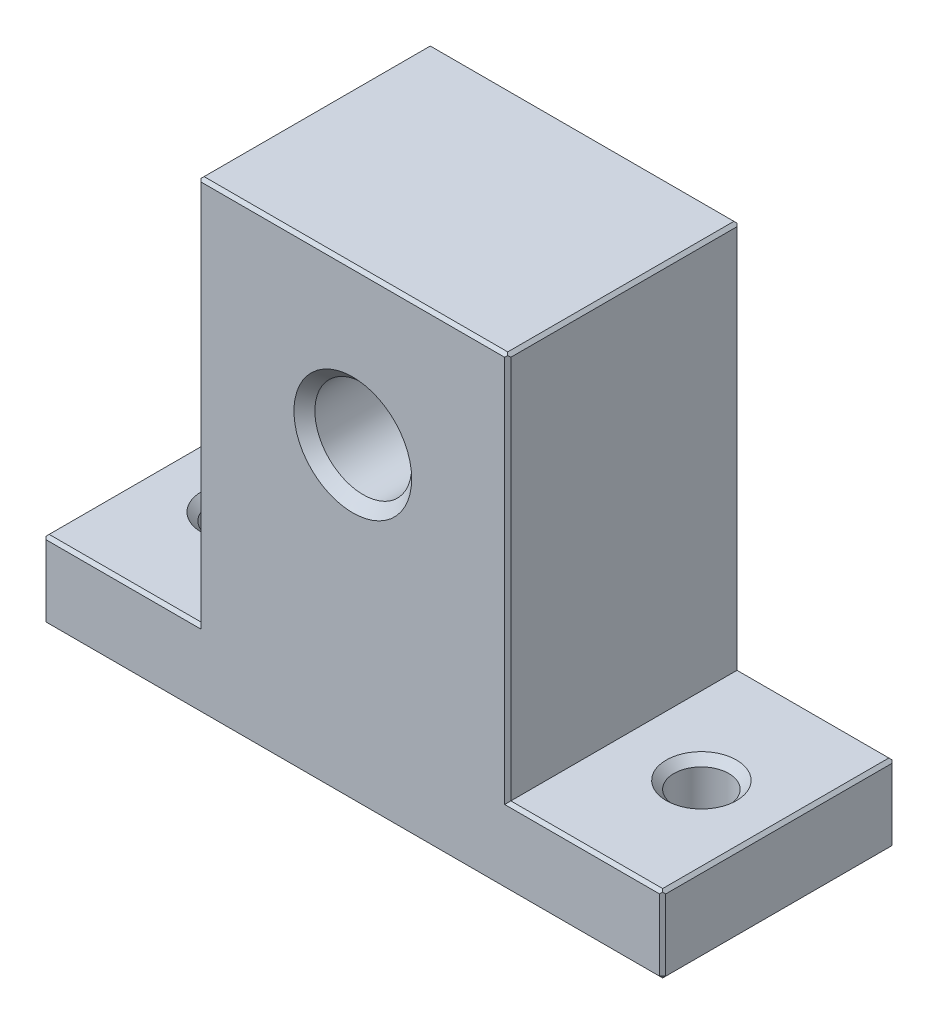
SolidWorks part; units mm, degrees
material "6061-T6 (SS)"
ref_plane "Front Plane" through (0, 0, 0) normal (0, 0, 1) x (1, 0, 0)
ref_plane "Top Plane" through (0, 0, 0) normal (0, 1, 0) x (1, 0, 0)
ref_plane "Right Plane" through (0, 0, 0) normal (1, 0, 0) x (0, 0, -1)
ref_axis "X Axis" through (88.99, 0, 0) along (-1, 0, 0)
ref_axis "Y Axis" through (0, 55, 0) along (0, -1, 0)
ref_axis "Z Axis" through (0, 0, -88.99) along (0, 0, 1)
sketch "Sketch1" plane through (0, 0, 0) normal (0, 1, 0) x (1, 0, 0)
  line L1 (-25.4, -9.525) -> (25.4, -9.525)
  line L2 (-25.4, -9.525) -> (-25.4, 9.525)
  line L3 (-25.4, 9.525) -> (25.4, 9.525)
  line L4 (25.4, -9.525) -> (25.4, 9.525)
  line L5 (0, 9.525) -> (0, -9.525) construction
  line L6 (-25.4, 0) -> (25.4, 0) construction
  line L7 (-12.7, -9.525) -> (12.7, -9.525)
  line L8 (-12.7, -9.525) -> (-12.7, 9.525)
  line L9 (-12.7, 9.525) -> (12.7, 9.525)
  line L10 (12.7, -9.525) -> (12.7, 9.525)
  line L11 (0, 9.525) -> (0, -9.525) construction
  line L12 (-12.7, 0) -> (12.7, 0) construction
  point P0 (0, 0)
  point P4 (0, 0)
  dimension "D1" = 19.05
  dimension "D2" = 50.8
  dimension "D3" = 25.4
extrude "Boss-Extrude1" add sketch "Sketch1" along normal blind 6.35 contours L1 L8 L3 L2 | L1 L10 L3 L8 | L10 L1 L4 L3 region at (-19.05, 0, 0) region at (0, 0, 0) region at (19.05, 0, 0)
extrude "Boss-Extrude2" add sketch "Sketch1<3>" along normal blind 38.1 contours L1 L10 L3 L8 region at (0, 0, 0)
sketch "Sketch1<3>" plane through (0, 0, 0) normal (0, 1, 0) x (1, 0, 0) same geometry as "Sketch1"
sketch "Sketch3" plane through (0, 0, 9.525) normal (0, 0, 1) x (1, 0, 0)
  line L0 (0, 0) -> (0, 25.4) construction
  point P1 (0, 25.4)
  point P13 (0, 25.4)
  dimension "D1" = 25.4
hole_wizard "3/8-16 Tapped Hole1" positions "Sketch3" profile "Sketch4" tap size "3/8-16" standard "ANSI Inch" end condition through all
sketch "Sketch4" plane through (0, 25.4, 9.525) normal (1, 0, 0) x (0, -1, 0)
  line L0 (0, 0) -> (0, 19.05)
  line L1 (0, 19.05) -> (4.826, 19.05)
  line L2 (3.9687, 18.1927) -> (3.9687, 0.8573)
  line L3 (3.9687, 0.8573) -> (4.826, 0)
  line L5 (4.826, 0) -> (0, 0)
  line L6 (-3.9687, 0.8572) -> (-4.826, 0) construction
  line L7 (4.826, 19.05) -> (3.9687, 18.1927)
  line L8 (-4.826, 19.05) -> (-3.9688, 18.1927) construction
  line L11 (0, -6.35) -> (0, 107.95) construction
  dimension "Thru Tap Drill Dia." = 7.9375
  dimension "Thru Tap Drill Depth" = 19.05
  dimension "Near C'Sink Dia." = 9.652
  dimension "Near C'Sink Angle" = 90
  dimension "Far C'Sink Dia." = 9.652
  dimension "Far C'Sink Angle" = 90
cosmetic thread "Hole Thread1" parameters "D2"=9.525
sketch "Sketch6" plane through (0, 38.1, 0) normal (0, 1, 0) x (1, 0, 0)
  line L0 (19.05, 0) -> (-19.05, 0)
  point P4 (0, 0)
  dimension "D1" = 38.1
sketch "Sketch9" plane through (0, 6.35, 0) normal (0, 1, 0) x (1, 0, 0)
  point P0 (-19.05, 0)
  point P3 (19.05, 0)
hole_wizard "#8 Clearance Hole1" positions "Sketch9" profile "Sketch8" hole size "#8" standard "ANSI Inch" end condition through all
sketch "Sketch8" plane through (-19.05, 6.35, 0) normal (1, 0, 0) x (0, 0, 1)
  line L0 (0, 0) -> (0, 6.35)
  line L1 (0, 6.35) -> (2.8829, 6.35)
  line L2 (2.2479, 5.715) -> (2.2479, 0.635)
  line L3 (2.2479, 0.635) -> (2.8829, 0)
  line L5 (2.8829, 0) -> (0, 0)
  line L6 (-2.2479, 0.635) -> (-2.8829, 0) construction
  line L7 (2.8829, 6.35) -> (2.2479, 5.715)
  line L8 (-2.8829, 6.35) -> (-2.2479, 5.715) construction
  line L11 (0, -6.35) -> (0, 107.95) construction
  dimension "Thru Hole Dia." = 4.4958
  dimension "Thru Hole Depth" = 6.35
  dimension "Near C'Sink Dia." = 5.7658
  dimension "Near C'Sink Angle" = 90
  dimension "Far C'Sink Dia." = 5.7658
  dimension "Far C'Sink Angle" = 90
chamfer "Chamfer1" distance 0.254 angle 45 10 edges at (-12.7, 38.1, 0) (0, 38.1, -9.525) (12.7, 38.1, 0) (0, 38.1, 9.525) (19.05, 6.35, -9.525) (25.4, 6.35, 0) (19.05, 6.35, 9.525) (-19.05, 6.35, -9.525) (-19.05, 6.35, 9.525) (-25.4, 6.35, 0)
chamfer "Chamfer2" distance 0.254 angle 45 12 edges at (25.4, 3.048, -9.525) (25.4, 3.048, 9.525) (-25.4, 3.048, -9.525) (-25.4, 3.048, 9.525) (-25.4, 0, 0) (0, 0, -9.525) (25.4, 0, 0) (0, 0, 9.525) (12.7, 21.971, -9.525) (12.7, 21.971, 9.525) (-12.7, 21.971, 9.525) (-12.7, 21.971, -9.525)
ref_axis "Hole Axis" through (0, 25.4, -34.9674) along (0, 0, 1)
